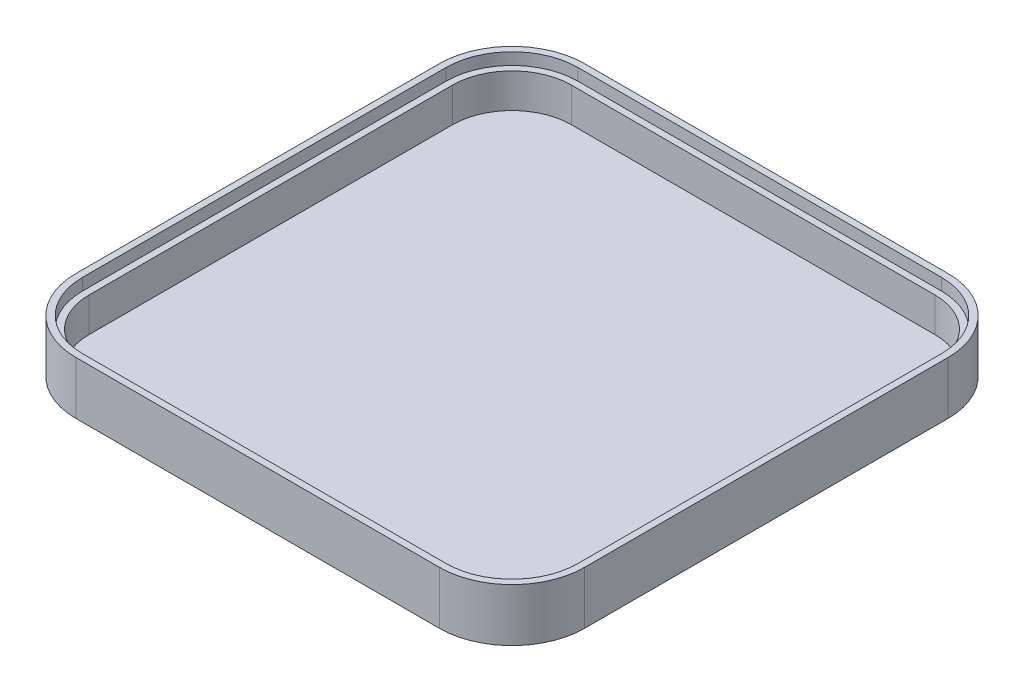
SolidWorks part; units mm, degrees
ref_plane "Front Plane" through (0, 0, 0) normal (0, 0, 1) x (1, 0, 0)
ref_plane "Top Plane" through (0, 0, 0) normal (0, 1, 0) x (1, 0, 0)
ref_plane "Right Plane" through (0, 0, 0) normal (1, 0, 0) x (0, 0, -1)
sketch "Sketch1" plane through (0, 0, 0) normal (0, 1, 0) x (1, 0, 0)
  line L0 (0, 75) -> (55, 75)
  line L1 (75, 55) -> (75, 0)
  line L2 (75, 0) -> (75, -55)
  line L3 (55, -75) -> (0, -75)
  line L4 (0, -75) -> (-55, -75)
  line L5 (-75, -55) -> (-75, 0)
  line L6 (-75, 0) -> (-75, 55)
  line L7 (-55, 75) -> (0, 75)
  line L8 (-55, 77) -> (0, 77)
  line L9 (0, 77) -> (55, 77)
  line L10 (77, 55) -> (77, 0)
  line L11 (77, 0) -> (77, -55)
  line L12 (55, -77) -> (0, -77)
  line L13 (0, -77) -> (-55, -77)
  line L14 (-77, -55) -> (-77, 0)
  line L15 (-77, 0) -> (-77, 55)
  arc A0 (55, 75) -> (75, 55) centre (55, 55) cw
  arc A1 (75, -55) -> (55, -75) centre (55, -55) cw
  arc A2 (-55, -75) -> (-75, -55) centre (-55, -55) cw
  arc A3 (-75, 55) -> (-55, 75) centre (-55, 55) cw
  arc A4 (55, 77) -> (77, 55) centre (55, 55) cw
  arc A5 (77, -55) -> (55, -77) centre (55, -55) cw
  arc A6 (-55, -77) -> (-77, -55) centre (-55, -55) cw
  arc A7 (-77, 55) -> (-55, 77) centre (-55, 55) cw
  point P24 (0, 0)
  dimension "D1" = 75
  dimension "D2" = 75
  dimension "D3" = 20
  dimension "D5" = 2
  dimension "D4" = 4
extrude "Boss-Extrude2" add sketch "Sketch1" along normal blind 14
sketch "Sketch4" plane through (0, 0, 0) normal (0, 1, 0) x (1, 0, 0)
  line L20 (55, 73) -> (-55, 73)
  line L21 (73, -55) -> (73, 55)
  line L22 (-55, -73) -> (55, -73)
  line L23 (-73, 55) -> (-73, -55)
  line L24 (55, 73) -> (-55, 73)
  line L25 (73, -55) -> (73, 55)
  line L26 (-55, -73) -> (55, -73)
  line L27 (-73, 55) -> (-73, -55)
  line L44 (55, 75) -> (-55, 75)
  line L45 (75, -55) -> (75, 55)
  line L46 (-55, -75) -> (55, -75)
  line L47 (-75, 55) -> (-75, -55)
  line L48 (55, 75) -> (-55, 75)
  line L49 (75, -55) -> (75, 55)
  line L50 (-55, -75) -> (55, -75)
  line L51 (-75, 55) -> (-75, -55)
  arc A24 (73, 55) -> (55, 73) centre (55, 55) ccw
  arc A25 (55, -73) -> (73, -55) centre (55, -55) ccw
  arc A26 (-73, -55) -> (-55, -73) centre (-55, -55) ccw
  arc A27 (-55, 73) -> (-73, 55) centre (-55, 55) ccw
  arc A28 (73, 55) -> (55, 73) centre (55, 55) ccw
  arc A29 (55, -73) -> (73, -55) centre (55, -55) ccw
  arc A30 (-73, -55) -> (-55, -73) centre (-55, -55) ccw
  arc A31 (-55, 73) -> (-73, 55) centre (-55, 55) ccw
  arc A52 (75, 55) -> (55, 75) centre (55, 55) ccw
  arc A53 (55, -75) -> (75, -55) centre (55, -55) ccw
  arc A54 (-75, -55) -> (-55, -75) centre (-55, -55) ccw
  arc A55 (-55, 75) -> (-75, 55) centre (-55, 55) ccw
  arc A56 (75, 55) -> (55, 75) centre (55, 55) ccw
  arc A57 (55, -75) -> (75, -55) centre (55, -55) ccw
  arc A58 (-75, -55) -> (-55, -75) centre (-55, -55) ccw
  arc A59 (-55, 75) -> (-75, 55) centre (-55, 55) ccw
  dimension "D1" = 2
  dimension "D2" = 0
extrude "Boss-Extrude3" add sketch "Sketch4" along normal blind 10.4
sketch "Sketch5" plane through (0, 0, 0) normal (0, -1, 0) x (1, 0, 0)
  line L8 (-55, -77) -> (55, -77)
  line L9 (77, -55) -> (77, 55)
  line L10 (55, 77) -> (-55, 77)
  line L11 (-77, 55) -> (-77, -55)
  line L12 (-55, -77) -> (55, -77)
  line L13 (77, -55) -> (77, 55)
  line L14 (55, 77) -> (-55, 77)
  line L15 (-77, 55) -> (-77, -55)
  arc A8 (-77, -55) -> (-55, -77) centre (-55, -55) ccw
  arc A9 (55, -77) -> (77, -55) centre (55, -55) ccw
  arc A10 (77, 55) -> (55, 77) centre (55, 55) ccw
  arc A11 (-55, 77) -> (-77, 55) centre (-55, 55) ccw
  arc A12 (-77, -55) -> (-55, -77) centre (-55, -55) ccw
  arc A13 (55, -77) -> (77, -55) centre (55, -55) ccw
  arc A14 (77, 55) -> (55, 77) centre (55, 55) ccw
  arc A15 (-55, 77) -> (-77, 55) centre (-55, 55) ccw
  dimension "D1" = 0
extrude "Boss-Extrude4" add sketch "Sketch5" along normal blind 2
